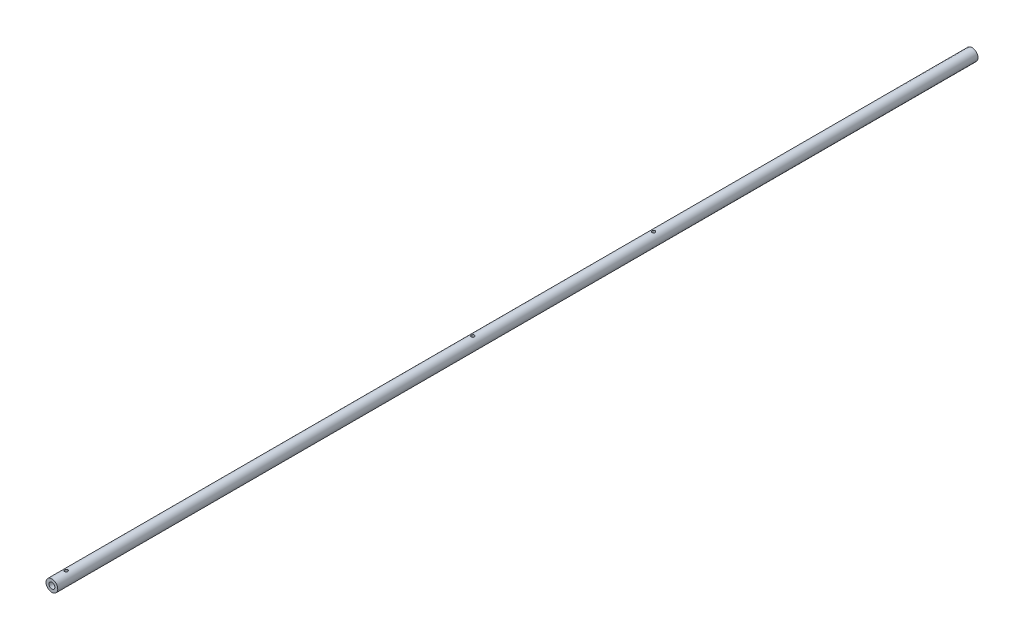
SolidWorks part; units mm, degrees
ref_plane "Front Plane" through (0, 0, 0) normal (0, 0, 1) x (1, 0, 0)
ref_plane "Top Plane" through (0, 0, 0) normal (0, 1, 0) x (1, 0, 0)
ref_plane "Right Plane" through (0, 0, 0) normal (1, 0, 0) x (0, 0, -1)
sketch "Sketch1" plane through (0, 0, 0) normal (0, 0, 1) x (1, 0, 0)
  circle A0 centre (0, 0) radius 3.9306
  circle A1 centre (0, 0) radius 7.8613
  dimension "D1" = 15.7226
  dimension "D2" = 7.8613
extrude "Rod" add sketch "Sketch1" along normal blind 1228.725
sketch "Sketch3" plane through (0, 0, 0) normal (0, 1, 0) x (1, 0, 0)
  line L0 (0, -425.45) -> (0, -962.025) construction
  line L1 (-7.8613, -1228.725) -> (7.8613, -1228.725) construction
  circle A0 centre (0, -425.45) radius 2.1082
  circle A4 centre (0, -666.75) radius 2.1082
  circle A5 centre (0, -1209.675) radius 2.1082
  dimension "D1" = 4.2164
  dimension "D6" = 4.2164
  dimension "D2" = 425.45
  dimension "D4" = 241.3
  dimension "D5" = 536.575
  dimension "D7" = 19.05
  dimension "D3" = 2
extrude "Holes" cut sketch "Sketch3" against normal through all both and the other way through all
ref_plane "Handle Location" through (0, 0, 962.025) normal (0, 0, 1) x (1, 0, 0)
equation "\"L\"= 48.375"
equation "\"D1@Rod\" = \"L\""
equation "\"N\"= 2"
equation "\"D3@Sketch3\"=\"N\""
equation "\"S\"= 9.5"
equation "\"D4@Sketch3\"=\"S\""
equation "\"O\"= 16.75"
equation "\"D2@Sketch3\"=\"O\""
equation "\"H\"= 21.125"
equation "\"D5@Sketch3\"=\"H\""
